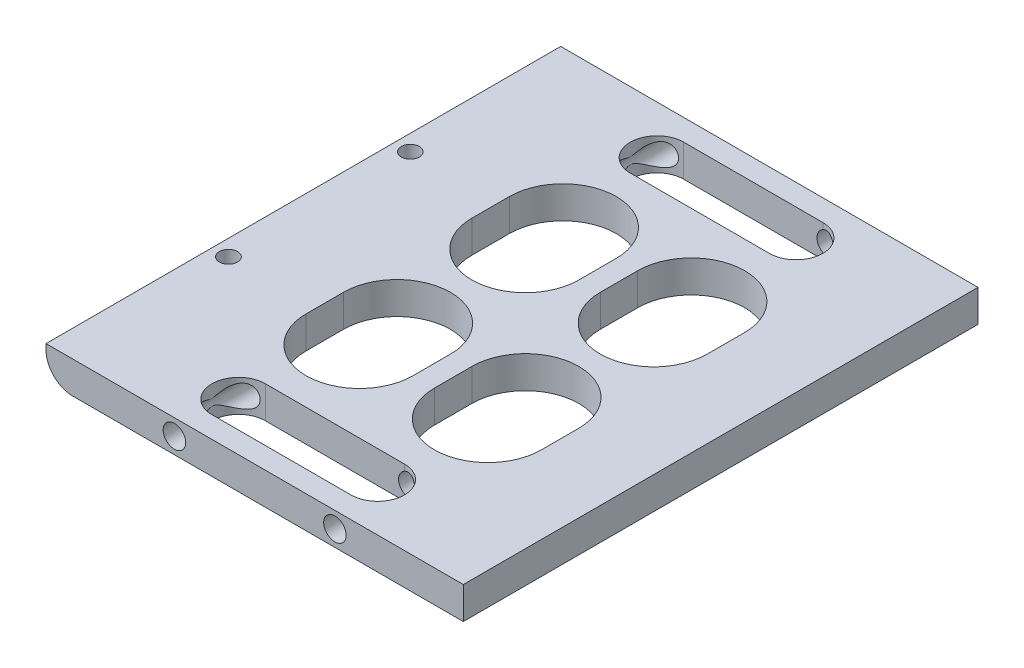
SolidWorks part; units mm, degrees
ref_plane "Front Plane" through (0, 0, 0) normal (1, 0, 0) x (0, 1, 0)
ref_plane "Top Plane" through (0, 0, 0) normal (0, 0, 1) x (0, 1, 0)
ref_plane "Right Plane" through (0, 0, 0) normal (0, 1, 0) x (-1, 0, 0)
sketch "Sketch1" plane through (0, 0, 0) normal (0, 1, 0) x (-1, 0, 0)
  line L0 (-49.4324, 0) -> (-18.4787, 0) construction
  line L1 (0, 0) -> (78, 0)
  line L2 (0, 0) -> (0, 96.2019)
  line L3 (0, 96.2019) -> (78, 96.2019)
  line L4 (78, 0) -> (78, 96.2019)
  point P33 (78, 96.2019)
  dimension "D1" = 96.2019
  dimension "D2" = 78
extrude "Boss-Extrude1" add sketch "Sketch1" along normal blind 6
sketch "Sketch2" plane through (0, 0, 0) normal (0, -1, 0) x (-1, 0, 0)
  line L0 (75, -31.101) -> (75, -65.1009) construction
  line L1 (78, 0) -> (78, -96.2019) construction
  line L2 (78, 0) -> (78, -96.2019)
  line L3 (78, 0) -> (72, 0)
  line L4 (0, 0) -> (78, 0) construction
  line L5 (72, 0) -> (72, -96.2019)
  line L6 (78, -96.2019) -> (0, -96.2019) construction
  line L7 (72, -96.2019) -> (78, -96.2019)
  line L8 (78, -48.1009) -> (72, -48.1009) construction
  circle A0 centre (75, -65.1009) radius 1.5
  circle A1 centre (75, -31.101) radius 1.5
  point P19 (75, -48.1009)
  dimension "D1" = 3
  dimension "D2" = 34
  dimension "D3" = 6
extrude "Cut-Extrude2" cut sketch "Sketch2" against normal through all contours A1 | A0 region at (-75, 0, 65.1009) region at (-75, 0, 31.101)
sketch "Sketch3" plane through (0, 0, 0) normal (0, 0, -1) x (1, 0, 0)
  line L0 (-39, 0) -> (-39, -6) construction
  line L1 (-54, -3) -> (-24, -3) construction
  line L2 (0, 0) -> (-78, 0) construction
  line L3 (0, -6) -> (-78, -6) construction
  circle A0 centre (-54, -3) radius 2.1
  circle A1 centre (-24, -3) radius 2.1
  point P6 (-39, -3)
  dimension "D1" = 4.2
  dimension "D2" = 30
extrude "Cut-Extrude3" cut sketch "Sketch3" against normal blind 18
extrude "Cut-Extrude4" cut sketch "Sketch3<2>" along normal blind 18 from surface starting at face at (-39, 3, 96.2019)
sketch "Sketch3<2>" plane through (0, 0, 0) normal (0, 0, -1) x (1, 0, 0) same geometry as "Sketch3"
fillet "Fillet1" radius 5 1 edges at (-78, 0, 48.1009)
sketch "Sketch4" plane through (0, 0, 0) normal (0, -1, 0) x (1, 0, 0)
  line L0 (-73, 48.1009) -> (0, 48.1009) construction
  line L5 (-73, 96.2019) -> (-73, 0) construction
  line L6 (0, 96.2019) -> (0, 0) construction
  line L7 (-36.5, 96.2019) -> (-36.5, 0) construction
  line L8 (-73, 96.2019) -> (0, 96.2019) construction
  line L9 (0, 0) -> (-73, 0) construction
  line L38 (-51, 87.2019) -> (-25, 87.2019) construction
  line L41 (-51, 92.2019) -> (-25, 92.2019)
  line L44 (-51, 82.2019) -> (-25, 82.2019)
  line L45 (-48.5, 29.1009) -> (-48.5, 36.1009) construction
  line L46 (-58.5, 29.1009) -> (-58.5, 36.1009)
  line L47 (-38.5, 29.1009) -> (-38.5, 36.1009)
  line L48 (-48.5, 67.101) -> (-48.5, 60.1009) construction
  line L49 (-38.5, 67.101) -> (-38.5, 60.1009)
  line L50 (-58.5, 67.101) -> (-58.5, 60.1009)
  line L51 (-24.5, 29.1009) -> (-24.5, 36.1009) construction
  line L52 (-14.5, 29.1009) -> (-14.5, 36.1009)
  line L53 (-34.5, 29.1009) -> (-34.5, 36.1009)
  line L54 (-24.5, 67.101) -> (-24.5, 60.1009) construction
  line L55 (-34.5, 67.101) -> (-34.5, 60.1009)
  line L56 (-14.5, 67.101) -> (-14.5, 60.1009)
  line L57 (-48.5, 50.1009) -> (-24.5, 50.1009) construction
  line L58 (-51, 9) -> (-25, 9) construction
  line L59 (-51, 4) -> (-25, 4)
  line L60 (-51, 14) -> (-25, 14)
  arc A20 (-51, 92.2019) -> (-51, 82.2019) centre (-51, 87.2019) ccw
  arc A21 (-25, 82.2019) -> (-25, 92.2019) centre (-25, 87.2019) ccw
  arc A22 (-58.5, 29.1009) -> (-38.5, 29.1009) centre (-48.5, 29.1009) ccw
  arc A23 (-38.5, 36.1009) -> (-58.5, 36.1009) centre (-48.5, 36.1009) ccw
  arc A24 (-38.5, 67.101) -> (-58.5, 67.101) centre (-48.5, 67.101) ccw
  arc A25 (-58.5, 60.1009) -> (-38.5, 60.1009) centre (-48.5, 60.1009) ccw
  arc A26 (-14.5, 29.1009) -> (-34.5, 29.1009) centre (-24.5, 29.1009) cw
  arc A27 (-34.5, 36.1009) -> (-14.5, 36.1009) centre (-24.5, 36.1009) cw
  arc A28 (-34.5, 67.101) -> (-14.5, 67.101) centre (-24.5, 67.101) cw
  arc A29 (-14.5, 60.1009) -> (-34.5, 60.1009) centre (-24.5, 60.1009) cw
  arc A30 (-51, 4) -> (-51, 14) centre (-51, 9) cw
  arc A31 (-25, 14) -> (-25, 4) centre (-25, 9) cw
  point P2 (-38, 87.2019)
  point P19 (-48.5, 32.6009)
  point P26 (-48.5, 63.601)
  point P41 (-38, 9)
  point P45 (-24.5, 32.6009)
  point P52 (-24.5, 63.601)
  dimension "D6" = 4
  dimension "D7" = 25
  dimension "D8" = 22
  dimension "D1" = 7
  dimension "D2" = 20
  dimension "D3" = 4
  dimension "D4" = 2
  dimension "D5" = 10
extrude "Cut-Extrude5" cut sketch "Sketch4" against normal blind 10
hole_wizard "CSK for M3 SFHCS2" positions "Sketch7" profile "Sketch8" countersink size "M3" standard "ANSI Metric" end condition through all
sketch "Sketch7" plane through (0, 0, 0) normal (0, -1, 0) x (-1, 0, 0)
  point P4 (75, -31.101)
  point P8 (75, -65.1009)
sketch "Sketch8" plane through (-75, 0, 31.101) normal (1, 0, 0) x (0, 0, -1)
  line L0 (0, 0) -> (0, 6)
  line L1 (0, 6) -> (1.7, 6)
  line L2 (1.7, 6) -> (1.7, 1.86)
  line L3 (1.7, 1.86) -> (3.56, 0)
  line L5 (3.56, 0) -> (0, 0)
  line L6 (-1.7, 1.86) -> (-3.56, 0) construction
  line L11 (0, -6.35) -> (0, 107.95) construction
  dimension "Thru Hole Dia." = 3.4
  dimension "Thru Hole Depth" = 6
  dimension "Near C'Sink Dia." = 7.12
  dimension "Near C'Sink Angle" = 90
equation "\"MotorDriverLength\"= 60mm"
equation "\"MotorLength\"= 60"
equation "\"MotorDriverWidth\"=44"
equation "\"MotorWidth\"= 37"
equation "\"InnerWallThickness\"=3"
equation "\"BatteryWidth\"= 60"
equation "\"OuterWallThickness\" = 6"
equation "\"CompartmentHeight\"=37"
equation "\"CompartmentWidth\"= \"MotorDriverLength\""
equation "\"MotorDiameter\"=37"
equation "\"BatteryHeight\"=24.2019"
equation "\"MotorDriverHeight\"=28"
equation "\"CircuitHeight\"=30"
equation "\"FanThickness\"= 10"
equation "\"FanHeight\"=50"
equation "\"MotorShaftHole\"=12"
equation "\"BearingBore\"=10"
equation "\"MinShinWidth\"= 20"
equation "\"ShinThickness\"=10"
equation "\"PivotDistance\"=30"
equation "\"ThighLength\"= 150"
equation "\"KneeLength\" =80"
equation "\"HipBore\"=27"
equation "\"ThighThickness\"=10"
equation "\"MaxBending\"=135"
equation "\"ShinLength\"=120"
equation "\"BearingDiameter\"= 10"
equation "\"CircuitLength\"=50"
equation "\"ChessisInnerWidth\"= \"OuterWallThickness\" * 2 + \"MotorDriverLength\" + \"MotorDiameter\" + \"InnerWallThickness\" * 3 + \"CircuitLength\""
equation "\"ChessisHeight\"= \"BatteryHeight\" + 10 + \"InnerWallThickness\" + \"MotorDiameter\" + 10 + \"OuterWallThickness\" * 2"
equation "\"ChassisWidth\"= \"MotorDriverWidth\"*4+30"
equation "\"D1@Sketch1\"=\"ChessisHeight\""
equation "\"D2@Sketch1\"=\"MotorWidth\"+\"FanThickness\"*2 +\"OuterWallThickness\"+15"
equation "\"D1@Boss-Extrude1\"=\"OuterWallThickness\""
equation "\"D2@Sketch2\"=17*2"
